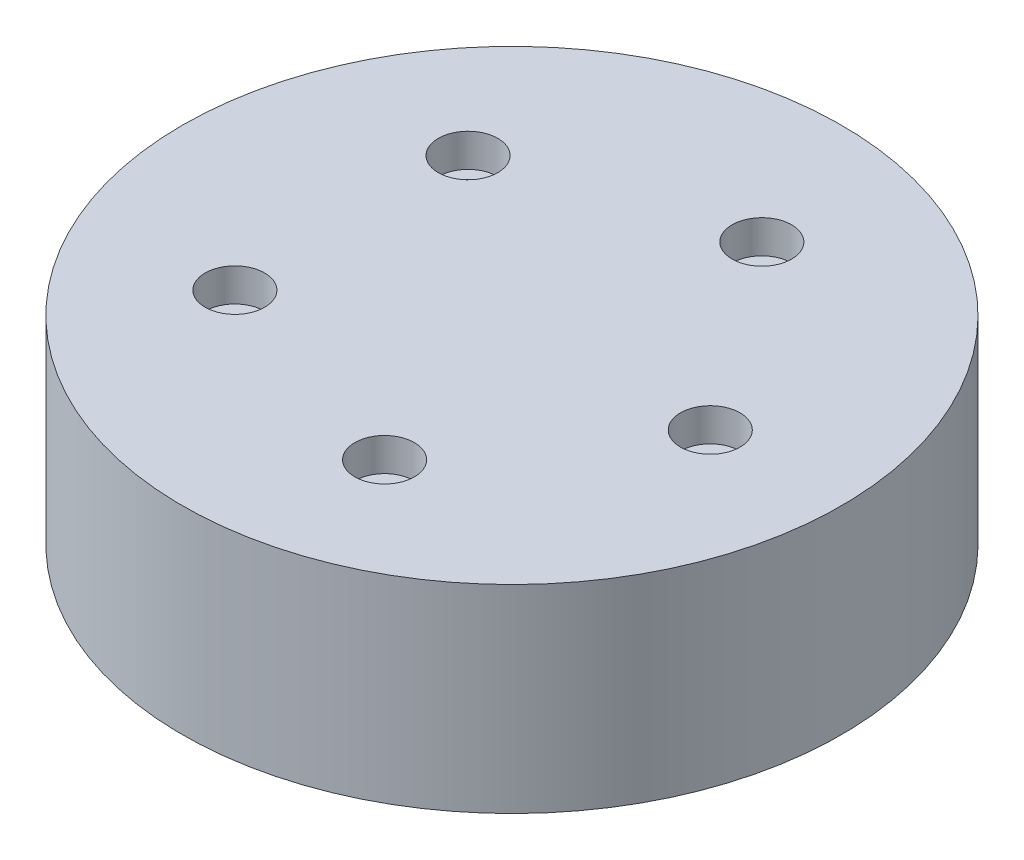
SolidWorks part; units mm, degrees
ref_plane "Front Plane" through (0, 0, 0) normal (0, 0, 1) x (1, 0, 0)
ref_plane "Top Plane" through (0, 0, 0) normal (0, 1, 0) x (1, 0, 0)
ref_plane "Right Plane" through (0, 0, 0) normal (1, 0, 0) x (0, 0, -1)
sketch "Sketch3" plane through (0, 15, 0) normal (0, 1, 0) x (1, 0, 0)
  circle A0 centre (-1.2, 0) radius 24.925
  circle A1 centre (13.8, 0) radius 1.3
  circle A6 centre (-1.2, 0) radius 15
  circle A7 centre (-1.2, 0) radius 15
  circle A8 centre (3.4353, -14.2658) radius 1.3
  circle A9 centre (-1.2, 0) radius 15
  circle A10 centre (-13.3353, -8.8168) radius 1.3
  circle A11 centre (-1.2, 0) radius 15
  circle A12 centre (-13.3353, 8.8168) radius 1.3
  circle A13 centre (-1.2, 0) radius 15
  circle A14 centre (3.4353, 14.2658) radius 1.3
  dimension "D1" = 49.85
  dimension "D2" = 5
  dimension "D3" = 2.6
extrude "Boss-Extrude1" add sketch "Sketch3" along normal blind 5 and the other way blind 10 contours A14 A6 A12 A10 A8 A1 | A0 A14 A6 A1 A8 A10 A12 region at (-25.42, 15, 0) region at (-1.2, 15, 0)
sketch "Sketch6" plane through (0, 5, 0) normal (0, -1, 0) x (1, 0, 0)
  circle A0 centre (-1.2, 0) radius 15
  circle A1 centre (13.8, 0) radius 1.65
  circle A2 centre (3.4353, -14.2658) radius 1.65
  circle A3 centre (-13.3353, -8.8168) radius 1.65
  circle A4 centre (-13.3353, 8.8168) radius 1.65
  circle A5 centre (3.4353, 14.2658) radius 1.65
  dimension "D1" = 5
  dimension "D2" = 3.3
extrude "Cut-Extrude1" cut sketch "Sketch6" against normal blind 5 contours A4 | A5 | A1 | A3 | A2
hole_wizard "CBORE for M2.5 SHCS1" positions "Sketch7" profile "Sketch8" counterbore size "M2.5" standard "ANSI Metric" end condition through all
sketch "Sketch7" plane through (0, 20, 0) normal (0, 1, 0) x (1, 0, 0)
  point P0 (13.8, 0)
  point P3 (3.4353, -14.2658)
  point P6 (-13.3353, -8.8168)
  point P9 (3.4353, 14.2658)
  point P12 (-13.3353, 8.8168)
sketch "Sketch8" plane through (13.8, 20, 0) normal (1, 0, 0) x (0, 0, 1)
  line L0 (0, 0) -> (0, 15)
  line L1 (0, 15) -> (1.25, 15)
  line L3 (1.25, 15) -> (1.25, 2.5)
  line L4 (1.25, 2.5) -> (2.25, 2.5)
  line L5 (2.25, 2.5) -> (2.25, 0)
  line L7 (2.25, 0) -> (0, 0)
  line L11 (0, -6.35) -> (0, 107.95) construction
  dimension "Thru Hole Dia." = 2.5
  dimension "Thru Hole Depth" = 15
  dimension "C'Bore Dia." = 4.5
  dimension "C'Bore Depth" = 2.5
